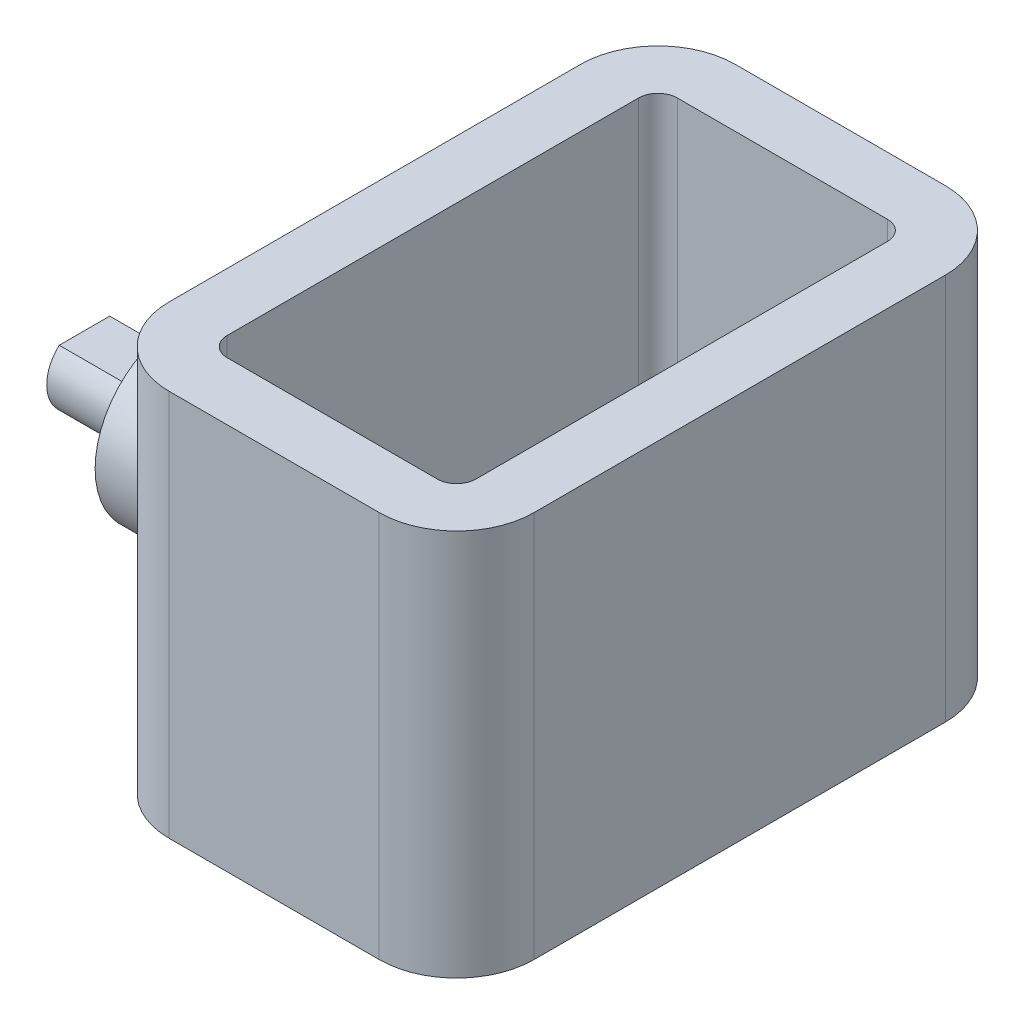
SolidWorks part; units mm, degrees
ref_plane "Front Plane" through (0, 0, 0) normal (0, 0, 1) x (1, 0, 0)
ref_plane "Top Plane" through (0, 0, 0) normal (0, 1, 0) x (1, 0, 0)
ref_plane "Right Plane" through (0, 0, 0) normal (1, 0, 0) x (0, 0, -1)
sketch "Sketch1" plane through (0, 0, 0) normal (0, 1, 0) x (1, 0, 0)
  line L0 (-5.425, 14.625) -> (5.425, 14.625)
  line L1 (-5.425, 11.625) -> (5.425, 11.625)
  line L2 (-6.425, 10.625) -> (-6.425, -10.625)
  line L3 (-5.425, -11.625) -> (5.425, -11.625)
  line L4 (6.425, 10.625) -> (6.425, -10.625)
  line L5 (-6.425, 11.625) -> (6.425, -11.625) construction
  line L6 (-6.425, -11.625) -> (6.425, 11.625) construction
  line L7 (9.425, 10.625) -> (9.425, -10.625)
  line L8 (-5.425, -14.625) -> (5.425, -14.625)
  line L9 (-9.425, 10.625) -> (-9.425, -10.625)
  arc A0 (-6.425, -10.625) -> (-5.425, -11.625) centre (-5.425, -10.625) ccw
  arc A1 (5.425, -11.625) -> (6.425, -10.625) centre (5.425, -10.625) ccw
  arc A2 (5.425, 11.625) -> (6.425, 10.625) centre (5.425, 10.625) cw
  arc A3 (-5.425, 11.625) -> (-6.425, 10.625) centre (-5.425, 10.625) ccw
  arc A4 (5.425, 14.625) -> (9.425, 10.625) centre (5.425, 10.625) cw
  arc A5 (5.425, -14.625) -> (9.425, -10.625) centre (5.425, -10.625) ccw
  arc A6 (-9.425, -10.625) -> (-5.425, -14.625) centre (-5.425, -10.625) ccw
  arc A7 (-5.425, 14.625) -> (-9.425, 10.625) centre (-5.425, 10.625) ccw
  point P0 (0, 0)
  dimension "D3" = 1
  dimension "D1" = 12.85
  dimension "D2" = 23.25
  dimension "D4" = 3
extrude "Boss-Extrude1" add sketch "Sketch1" along normal blind 20
sketch "Sketch2" plane through (-9.425, 0, 0) normal (-1, 0, 0) x (0, 0, 1)
  line L0 (-10.625, 0) -> (10.625, 0) construction
  line L1 (1.3038, 5.9) -> (-1.3038, 5.9)
  circle A0 centre (0, 4.45) radius 4.45
  circle A1 centre (0, 4.45) radius 1.95
  dimension "D1" = 8.9
  dimension "D2" = 3.9
  dimension "D3" = 0.5
extrude "Boss-Extrude2" add sketch "Sketch2" along normal blind 10 contours A0 A1 | L1 A1 region at (-9.425, 6.1024, 0) region at (-9.425, 4.45, -4.3241)
extrude "Boss-Extrude3" add sketch "Sketch2<4>" along normal blind 15 contours L1 A1 region at (-9.425, 4.3163, 0)
sketch "Sketch2<4>" plane through (-9.425, 0, 0) normal (-1, 0, 0) x (0, 0, 1) same geometry as "Sketch2"
